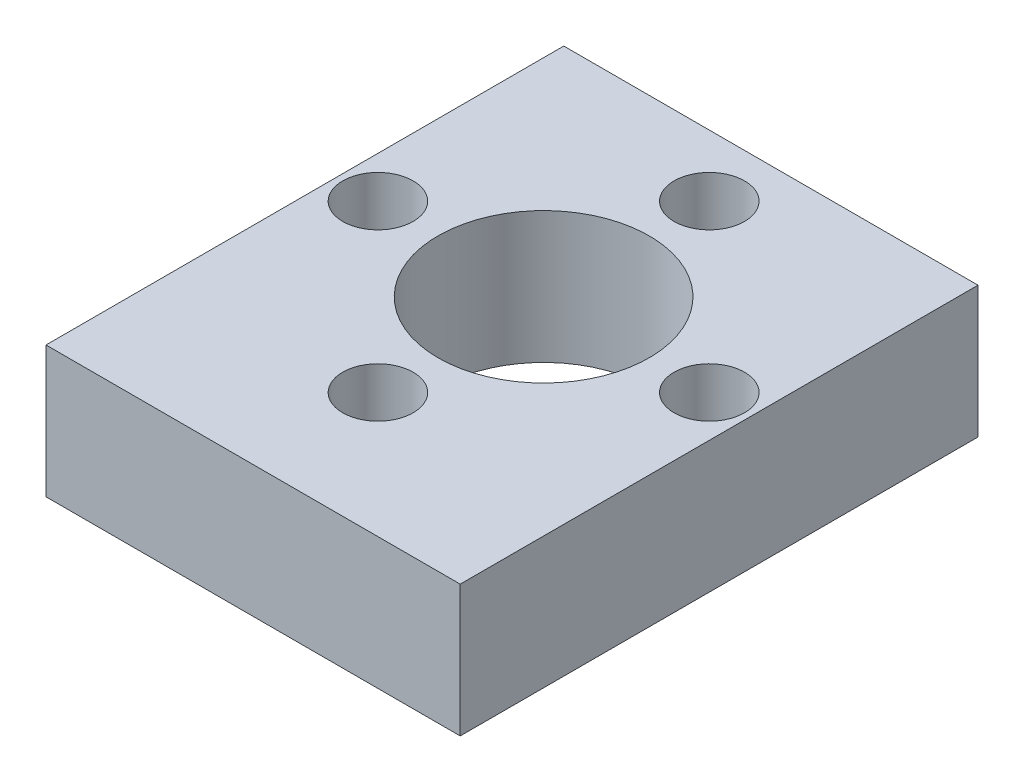
SolidWorks part; units mm, degrees
ref_plane "Front Plane" through (0, 0, 0) normal (0, 0, 1) x (1, 0, 0)
ref_plane "Top Plane" through (0, 0, 0) normal (0, 1, 0) x (1, 0, 0)
ref_plane "Right Plane" through (0, 0, 0) normal (1, 0, 0) x (0, 0, -1)
sketch "Sketch1" plane through (0, 0, 0) normal (0, 1, 0) x (1, 0, 0)
  line L1 (-10, -12.5) -> (10, -12.5)
  line L2 (-10, -12.5) -> (-10, 12.5)
  line L3 (-10, 12.5) -> (10, 12.5)
  line L4 (10, -12.5) -> (10, 12.5)
  line L5 (-10, -12.5) -> (10, 12.5) construction
  line L6 (-10, 12.5) -> (10, -12.5) construction
  circle A0 centre (0, 1.5262) radius 5.1
  point P0 (0, 1.5262)
  dimension "D1" = 10.2
  dimension "D2" = 20
  dimension "D3" = 25
  dimension "D4" = 1.5262
extrude "Boss-Extrude1" add sketch "Sketch1" along normal blind 6.35 contours L1 L4 L3 L2 A0 region at (-9.6798, 0, 0)
sketch "Sketch2" plane through (0, 6.35, 0) normal (0, 1, 0) x (1, 0, 0)
  circle A0 centre (0, 1.5262) radius 8 construction
  point P2 (0, 9.5262)
  point P4 (8, 1.5262)
  point P5 (0, -6.4738)
  point P6 (-8, 1.5262)
  dimension "D1" = 8
hole_wizard "M3 Clearance Hole1" positions "Sketch2" profile "Sketch3" hole size "M3" standard "ANSI Metric" end condition through all
sketch "Sketch3" plane through (-8, 6.35, -1.5262) normal (1, 0, 0) x (0, 0, 1)
  line L0 (0, 0) -> (0, 6.35)
  line L1 (0, 6.35) -> (1.7, 6.35)
  line L2 (1.7, 6.35) -> (1.7, 0)
  line L5 (1.7, 0) -> (0, 0)
  line L11 (0, -6.35) -> (0, 107.95) construction
  dimension "Thru Hole Dia." = 3.4
  dimension "Thru Hole Depth" = 6.35
sketch "Sketch4" plane through (0, 0, -12.5) normal (0, 0, -1) x (-1, 0, 0)
  line L0 (0, 0) -> (0, 6.35) construction
  line L1 (10, 6.35) -> (-10, 6.35) construction
  line L9 (-7.62, 3.175) -> (7.62, 3.175) construction
  point P5 (0, 3.175)
  point P47 (0, 3.175)
  dimension "D1" = 15.24
hole_wizard "Tap Drill for M3x0.5 Tap3" positions "Sketch7" profile "Sketch8" hole size "M3x0.5" standard "ANSI Metric"
sketch "Sketch7" plane through (0, 0, -12.5) normal (0, 0, -1) x (-1, 0, 0)
  point P0 (-7.62, 3.175)
  point P3 (7.62, 3.175)
sketch "Sketch8" plane through (7.62, 3.175, -12.5) normal (1, 0, 0) x (0, 1, 0)
  line L0 (0, 0) -> (0, 6.7511)
  line L1 (0, 6.7511) -> (1.25, 6)
  line L2 (1.25, 6) -> (1.25, 0)
  line L5 (1.25, 0) -> (0, 0)
  line L10 (0, 6.7511) -> (-1.25, 6) construction
  line L11 (0, -6.35) -> (0, 107.95) construction
  dimension "Hole Dia." = 2.5
  dimension "Hole Depth" = 6
  dimension "Drill Angle" = 118
